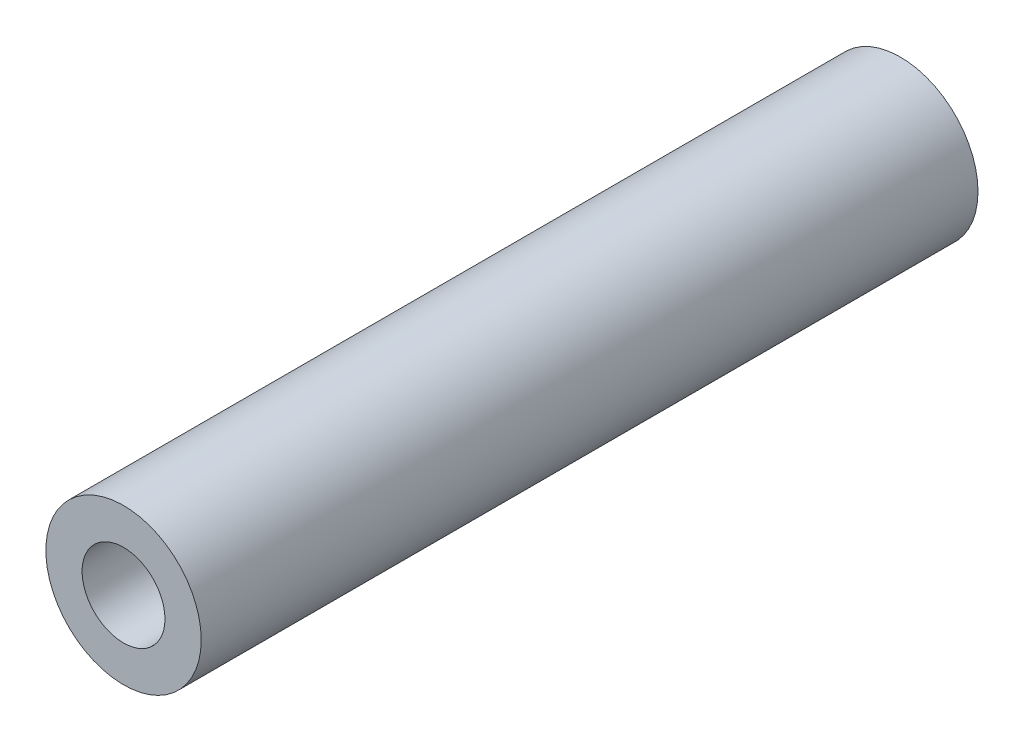
SolidWorks part; units mm, degrees
ref_plane "Front Plane" through (0, 0, 0) normal (0, 0, 1) x (1, 0, 0)
ref_plane "Top Plane" through (0, 0, 0) normal (0, 1, 0) x (1, 0, 0)
ref_plane "Right Plane" through (0, 0, 0) normal (1, 0, 0) x (0, 0, -1)
sketch "Sketch1" plane through (0, 0, 0) normal (0, 0, 1) x (1, 0, 0)
  circle A0 centre (0, 0) radius 3
  circle A1 centre (0, 0) radius 1.6
  dimension "OD" = 6
  dimension "ID" = 3.2
extrude "Extrude1" add sketch "Sketch1" along normal mid plane 30
sketch "Sketch2" plane through (0, 0, 0) normal (1, 0, 0) x (0, 0, -1)
  line L0 (-15, -1.6) -> (15, -1.6) construction
  line L3 (15, 1.6) -> (-15, 1.6) construction
  line L5 (-15, -1.6) -> (15, -1.6)
  line L6 (15, 1.6) -> (-15, 1.6)
sketch "Sketch4" plane through (0, 0, 15) normal (0, 0, 1) x (1, 0, 0)
  line L0 (0, 0) -> (-1.1314, 1.1314)
  line L1 (0, -3.3) -> (0, 3.3) construction
  circle A0 centre (0, 0) radius 1.6 construction
  dimension "D1" = 45
